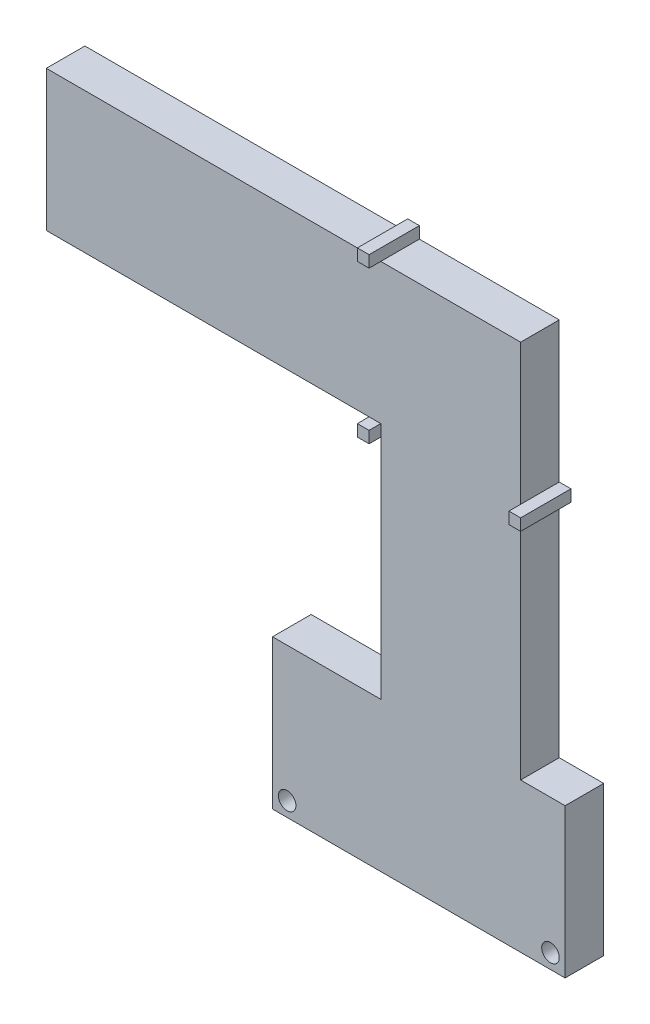
SolidWorks part; units mm, degrees
ref_plane "Ön Düzlem" through (0, 0, 0) normal (1, 0, 0) x (0, 1, 0)
ref_plane "Üst Düzlem" through (0, 0, 0) normal (0, 0, 1) x (0, 1, 0)
ref_plane "Sağ Düzlem" through (0, 0, 0) normal (0, 1, 0) x (-1, 0, 0)
sketch "Çizim1" plane through (0, 0, 0) normal (0, 0, 1) x (0, 1, 0)
  line L0 (0, 0) -> (171.5, 0)
  line L1 (0, 0) -> (0, 103)
  line L2 (0, 103) -> (63.3, 103)
  line L3 (171.5, 103) -> (171.5, 0)
  line L4 (25.5, 0) -> (25.5, 50)
  line L5 (0, 50) -> (25.5, 50)
  line L8 (90.3, 88.6603) -> (90.3, 69.7226) construction
  line L9 (17.5478, 31.5) -> (127.8031, 31.5) construction
  line L10 (17.5478, 7.6) -> (101.9694, 7.6) construction
  line L11 (66.3, 88.6603) -> (90.3, 88.6603) construction
  line L12 (17.5478, 31.5) -> (17.5478, 7.6) construction
  line L13 (25.5, 31.5) -> (66.3, 31.5)
  line L14 (66.3, 31.5) -> (66.3, 88.6603)
  line L15 (66.3, 88.6603) -> (90.3, 88.6603)
  line L16 (90.3, 88.6603) -> (90.3, 7.6)
  line L17 (90.3, 7.6) -> (25.5, 7.6)
  line L18 (66.3, 88.6603) -> (63.3, 88.6603)
  line L19 (63.3, 88.6603) -> (63.3, 103)
  line L20 (93.3, 103) -> (93.3, 88.6603)
  line L21 (93.3, 88.6603) -> (90.3, 88.6603)
  line L22 (93.3, 103) -> (171.5, 103)
  line L23 (66.3, 88.6603) -> (66.3, 61.9877) construction
  circle A1 centre (2.5, 47.5) radius 1.5
  circle A2 centre (2.5, 2.5) radius 1.5
  dimension "D1" = 66.3
  dimension "D2" = 90.3
  dimension "D3" = 171.5
  dimension "D4" = 7.6
  dimension "D5" = 31.5
  dimension "D6" = 47.5
  dimension "D7" = 103
  dimension "D8" = 63.3
extrude "Yükseklik-Ekstrüzyon1" add sketch "Çizim1" along normal blind 6.6 contours L5 L1 L0 L4 A2 A1 | L17 L16 L15 L14 L13 L4 region at (-25, 12.8649, 0) region at (-38.5878, 67.4823, 0)
sketch "Çizim3" plane through (0, 0, 0) normal (0, 0, 1) x (0, 1, 0)
  line L0 (66.3, 31.5) -> (66.3, 33.5)
  line L1 (66.3, 31.5) -> (66.3, 88.6603) construction
  line L2 (66.3, 33.5) -> (64.3, 33.5)
  line L3 (64.3, 33.5) -> (64.3, 31.5)
  line L4 (25.5, 31.5) -> (66.3, 31.5) construction
  line L5 (64.3, 31.5) -> (66.3, 31.5)
  line L6 (90.3, 33.5) -> (92.3, 33.5)
  line L7 (90.3, 88.6603) -> (90.3, 7.6) construction
  line L8 (92.3, 33.5) -> (92.3, 31.5)
  line L9 (92.3, 31.5) -> (90.3, 31.5)
  line L10 (90.3, 31.5) -> (90.3, 33.5)
  line L11 (64.3, 7.6) -> (64.3, 5.6)
  line L12 (90.3, 7.6) -> (25.5, 7.6) construction
  line L13 (64.3, 5.6) -> (66.3, 5.6)
  line L14 (66.3, 5.6) -> (66.3, 7.6)
  line L15 (64.3, 7.6) -> (66.3, 7.6)
  dimension "D1" = 64.3
extrude "Yükseklik-Ekstrüzyon3" add sketch "Çizim3" along normal up to surface (6.6 mm away) up to face at (-1, 2.5, 6.6)
sketch "Çizim4" plane through (0, 0, 6.6) normal (0, 0, 1) x (1, 0, 0)
  line L0 (-33.5, 92.3) -> (-33.5, 90.3)
  line L1 (-33.5, 90.3) -> (-31.5, 90.3)
  line L2 (-31.5, 90.3) -> (-31.5, 92.3)
  line L3 (-31.5, 92.3) -> (-33.5, 92.3)
  line L4 (-33.5, 66.3) -> (-33.5, 64.3)
  line L5 (-33.5, 66.3) -> (-33.5, 64.3) construction
  line L6 (-33.5, 66.3) -> (-88.6603, 66.3) construction
  line L7 (-33.5, 64.3) -> (-31.5, 64.3)
  line L8 (-31.5, 64.3) -> (-31.5, 66.3)
  line L9 (-31.5, 66.3) -> (-33.5, 66.3)
  line L10 (-5.6, 66.3) -> (-5.6, 64.3)
  line L11 (-5.6, 64.3) -> (-7.6, 64.3)
  line L12 (-7.6, 64.3) -> (-7.6, 66.3)
  line L13 (-7.6, 66.3) -> (-5.6, 66.3)
extrude "Yükseklik-Ekstrüzyon4" add sketch "Çizim4" along normal blind 2
